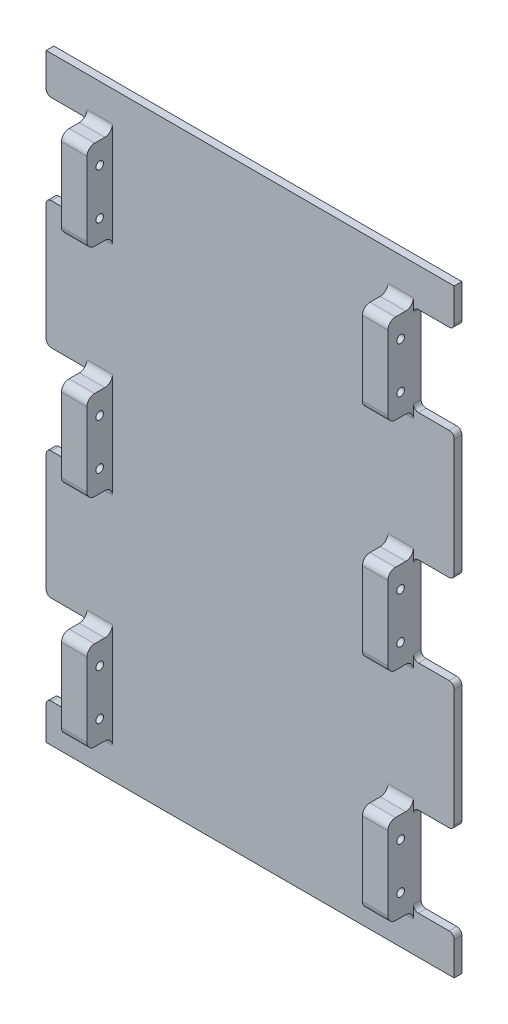
SolidWorks part; units mm, degrees
ref_plane "Front Plane" through (0, 0, 0) normal (0, 0, 1) x (1, 0, 0)
ref_plane "Top Plane" through (0, 0, 0) normal (0, 1, 0) x (1, 0, 0)
ref_plane "Right Plane" through (0, 0, 0) normal (1, 0, 0) x (0, 0, -1)
sketch "Sketch1" plane through (0, 0, 0) normal (0, 0, 1) x (1, 0, 0)
  line L0 (-64.0501, 42.5) -> (64, 42.5) construction
  line L5 (80, 25) -> (80, -25)
  line L8 (80, 25) -> (64, 25)
  line L9 (64, 60) -> (64, 25)
  line L10 (80, -60) -> (80, -75)
  line L11 (80, -60) -> (64, -60)
  line L13 (80, -25) -> (64, -25)
  line L14 (64, -60) -> (64, -25)
  line L15 (0, 75) -> (0, -75) construction
  line L25 (-64, -60) -> (-64, -25)
  line L26 (-80, -25) -> (-64, -25)
  line L27 (-80, -60) -> (-64, -60)
  line L28 (-80, -60) -> (-80, -75)
  line L29 (-64, 60) -> (-64, 25)
  line L30 (-80, 25) -> (-64, 25)
  line L32 (-80, 25) -> (-80, -25)
  line L35 (-80, -75) -> (80, -75)
  line L36 (0, 10) -> (0, 160) construction
  line L37 (-80, 160) -> (80, 160)
  line L38 (-80, 60) -> (-80, 110)
  line L39 (-80, 60) -> (-64, 60)
  line L40 (-80, 145) -> (-80, 160)
  line L41 (-80, 145) -> (-64, 145)
  line L42 (-80, 110) -> (-64, 110)
  line L43 (-64, 145) -> (-64, 110)
  line L44 (64, 145) -> (64, 110)
  line L45 (80, 110) -> (64, 110)
  line L46 (80, 145) -> (64, 145)
  line L47 (80, 145) -> (80, 160)
  line L48 (80, 60) -> (64, 60)
  line L49 (80, 60) -> (80, 110)
  point P27 (-64, 42.5)
extrude "Boss-Extrude1" add sketch "Sketch1" against normal blind 3
sketch "Sketch4" plane through (0, 0, 0) normal (0, 0, 1) x (1, 0, 0)
  line L0 (-64, -60) -> (-54, -60)
  line L5 (80, 0) -> (-80, 0) construction
  line L6 (64, 60) -> (54, 60)
  line L7 (64, 60) -> (64, 25)
  line L8 (64, 25) -> (54, 25)
  line L9 (54, 60) -> (54, 25)
  line L10 (80, -25) -> (80, 25) construction
  line L11 (-80, 25) -> (-80, -25) construction
  line L12 (54, -60) -> (54, -25)
  line L13 (64, -25) -> (54, -25)
  line L14 (64, -60) -> (64, -25)
  line L15 (64, -60) -> (54, -60)
  line L16 (0, 75) -> (0, -75) construction
  line L18 (-80, -75) -> (80, -75) construction
  line L19 (-64, -60) -> (-64, -25)
  line L20 (-64, -25) -> (-54, -25)
  line L21 (-54, -60) -> (-54, -25)
  line L22 (-54, 60) -> (-54, 25)
  line L23 (-64, 25) -> (-54, 25)
  line L24 (-64, 60) -> (-64, 25)
  line L25 (-64, 60) -> (-54, 60)
  line L26 (-80, 85) -> (80, 85) construction
  line L27 (-80, 110) -> (-80, 60) construction
  line L28 (80, 60) -> (80, 110) construction
  line L29 (-64, 110) -> (-54, 110)
  line L30 (-64, 110) -> (-64, 145)
  line L31 (-64, 145) -> (-54, 145)
  line L32 (-54, 110) -> (-54, 145)
  line L33 (54, 110) -> (54, 145)
  line L34 (64, 145) -> (54, 145)
  line L35 (64, 110) -> (64, 145)
  line L36 (64, 110) -> (54, 110)
extrude "Boss-Extrude3" add sketch "Sketch4" along normal blind 10
sketch "Sketch6" plane through (64, 0, 0) normal (1, 0, 0) x (0, 0, -1)
  line L0 (-5, -60) -> (-5, -25) construction
  line L1 (-10, -60) -> (0, -60) construction
  line L2 (-10, -25) -> (0, -25) construction
  line L3 (-5, -42.5) -> (3, -42.5) construction
  line L4 (3, -60) -> (3, -25) construction
  line L5 (3, 0) -> (-14.9966, 0) construction
  line L6 (3, -25) -> (3, 25) construction
  line L7 (-5, 42.5) -> (3, 42.5) construction
  line L8 (-5, 60) -> (-5, 25) construction
  line L9 (3, 85) -> (-14.9966, 85) construction
  line L10 (3, 60) -> (3, 110) construction
  line L11 (-5, 110) -> (-5, 145) construction
  line L12 (-5, 127.5) -> (3, 127.5) construction
  circle A0 centre (-5, -51.5) radius 1.5
  circle A1 centre (-5, -33.5) radius 1.5
  circle A2 centre (-5, 33.5) radius 1.5
  circle A3 centre (-5, 51.5) radius 1.5
  circle A4 centre (-5, 118.5) radius 1.5
  circle A5 centre (-5, 136.5) radius 1.5
extrude "Cut-Extrude1" cut sketch "Sketch6" against normal up to surface (128 mm away) up to face at (-64, -42.5, 2.3333)
fillet "Fillet2" radius 3 24 edges at (-59, -25, 0) (-59, -25, 10) (-59, -60, 10) (-59, -60, 0) (-59, 60, 0) (-59, 60, 10) (-59, 25, 10) (-59, 25, 0) (-59, 145, 10) (-59, 145, 0) (-59, 110, 0) (-59, 110, 10) (59, 145, 0) (59, 145, 10) (59, 110, 10) (59, 110, 0) (59, 60, 0) (59, 25, 0) (59, 25, 10) (59, 60, 10) (59, -25, 0) (59, -25, 10) (59, -60, 10) (59, -60, 0)
fillet "Fillet3" radius 2 24 edges at (80, -60, -1.5) (64, -60, -1.5) (80, -25, -1.5) (64, -25, -1.5) (80, 25, -1.5) (64, 25, -1.5) (64, 60, -1.5) (80, 60, -1.5) (80, 110, -1.5) (64, 110, -1.5) (64, 145, -1.5) (80, 145, -1.5) (-80, 145, -1.5) (-64, 145, -1.5) (-64, 110, -1.5) (-80, 110, -1.5) (-80, 60, -1.5) (-64, 60, -1.5) (-64, 25, -1.5) (-80, 25, -1.5) (-80, -25, -1.5) (-64, -25, -1.5) (-80, -60, -1.5) (-64, -60, -1.5)
